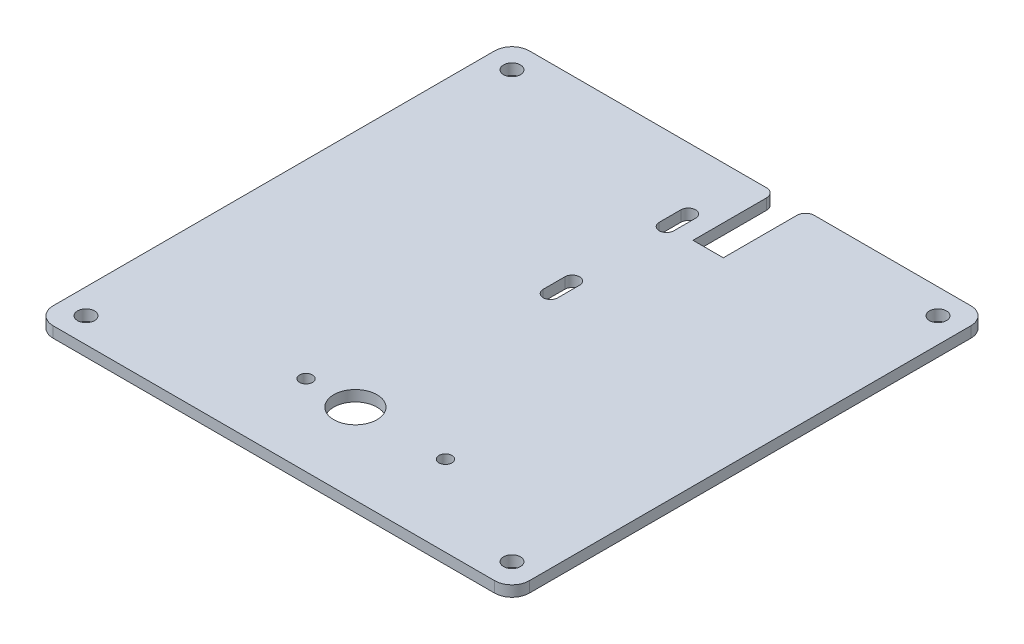
SolidWorks part; units mm, degrees
ref_plane "Front Plane" through (0, 0, 0) normal (0, 0, 1) x (1, 0, 0)
ref_plane "Top Plane" through (0, 0, 0) normal (0, 1, 0) x (1, 0, 0)
ref_plane "Right Plane" through (0, 0, 0) normal (1, 0, 0) x (0, 0, -1)
sketch "Sketch1" plane through (0, 0, 0) normal (0, 1, 0) x (1, 0, 0)
  line L5 (-69.85, -69.85) -> (69.85, -69.85)
  line L6 (-69.85, -69.85) -> (-69.85, 69.85)
  line L7 (-69.85, 69.85) -> (69.85, 69.85)
  line L8 (69.85, -69.85) -> (69.85, 69.85)
  line L9 (-69.85, -69.85) -> (69.85, 69.85) construction
  line L10 (-69.85, 69.85) -> (69.85, -69.85) construction
  line L11 (-69.85, 69.85) -> (69.85, 69.85)
  circle A0 centre (62.484, -62.484) radius 2.4892
  circle A1 centre (62.484, -62.484) radius 7.366 construction
  circle A8 centre (-62.484, 62.484) radius 2.4892
  circle A9 centre (-62.484, 62.484) radius 7.366 construction
  circle A10 centre (62.484, 62.484) radius 2.4892
  circle A11 centre (62.484, 62.484) radius 7.366 construction
  circle A12 centre (-62.484, -62.484) radius 2.4892
  circle A13 centre (-62.484, -62.484) radius 7.366 construction
  dimension "D3" = 14.732
  dimension "D4" = 4.9784
  dimension "D13" = 4.9784
  dimension "D14" = 14.732
  dimension "D15" = 4.9784
  dimension "D16" = 14.732
  dimension "D17" = 4.9784
  dimension "D18" = 14.732
  dimension "D11" = 139.7
  dimension "D12" = 139.7
extrude "Boss-Extrude1" add sketch "Sketch1" along normal blind 3.175 contours L5 L8 L7 L6 A12 A10 A8 A0 region at (0, 0, 0)
sketch "Sketch2" plane through (0, 3.175, 0) normal (0, 1, 0) x (1, 0, 0)
  line L0 (0, 123.83) -> (0, 28.326) construction
  line L1 (-69.85, 69.85) -> (69.85, 69.85)
  line L2 (-69.85, 69.85) -> (-69.85, 123.83) construction
  line L3 (-69.85, 123.83) -> (69.85, 123.83) construction
  line L4 (69.85, 69.85) -> (69.85, 123.83) construction
  line L5 (0, 11.308) -> (0, 45.344) construction
  line L6 (0, 45.344) -> (0, 51.694) construction
  line L7 (-2.1527, 45.344) -> (-2.1527, 51.694)
  line L8 (2.1527, 45.344) -> (2.1527, 51.694)
  line L9 (0, 11.308) -> (0, 17.658) construction
  line L10 (-2.1526, 11.308) -> (-2.1526, 17.658)
  line L11 (2.1527, 11.308) -> (2.1527, 17.658)
  line L12 (16.2727, 69.85) -> (7.3827, 69.85)
  line L13 (7.3827, 69.85) -> (16.2727, 69.85)
  line L14 (7.3827, 69.85) -> (7.3827, 45.72)
  line L15 (7.3827, 45.72) -> (16.2727, 45.72)
  line L16 (16.2727, 69.85) -> (16.2727, 45.72)
  arc A0 (-2.1527, 45.344) -> (2.1527, 45.344) centre (0, 45.344) ccw
  arc A1 (2.1527, 51.694) -> (-2.1527, 51.694) centre (0, 51.694) ccw
  arc A2 (-2.1526, 11.308) -> (2.1527, 11.308) centre (0, 11.308) ccw
  arc A3 (2.1527, 17.658) -> (-2.1526, 17.658) centre (0, 17.658) ccw
  point P10 (0, 48.519)
  point P16 (0, 14.483)
  dimension "D6" = 4.3053
  dimension "D7" = 4.3053
  dimension "D1" = 95.504
  dimension "D2" = 53.98
  dimension "D3" = 34.036
  dimension "D4" = 6.35
  dimension "D5" = 6.35
  dimension "D8" = 5.23
  dimension "D9" = 8.89
  dimension "D10" = 24.13
extrude "Cut-Extrude2" cut sketch "Sketch2" against normal up to surface (3.175 mm away) contours L16 L1 L14 L15 | A0 L8 A1 L7 | A3 L10 A2 L11 region at (11.8277, 3.175, -57.785) up to face at (-62.484, 0, 64.9732)
sketch "Sketch3" plane through (0, 3.175, 0) normal (0, 1, 0) x (1, 0, 0)
  line L0 (69.85, -69.85) -> (69.85, 69.85) construction
  line L1 (-69.85, -69.85) -> (69.85, -69.85) construction
  line L2 (-69.85, -69.85) -> (-69.85, -46.1981) construction
  line L3 (-69.85, -46.1981) -> (69.85, -46.1981) construction
  line L4 (69.85, -69.85) -> (69.85, -46.1981) construction
  circle A0 centre (-14.224, -46.1981) radius 1.905
  circle A1 centre (26.67, -46.1981) radius 1.905
  circle A2 centre (0.254, -46.1981) radius 6.35
  dimension "D4" = 3.81
  dimension "D5" = 3.81
  dimension "D6" = 12.7
  dimension "D1" = 23.6519
  dimension "D2" = 40.894
  dimension "D3" = 14.478
  dimension "D7" = 43.18
extrude "Cut-Extrude4" cut sketch "Sketch3" against normal up to surface (3.175 mm away) contours A2 | A1 | A0 region at (26.67, 3.175, 46.1981) region at (0.254, 3.175, 46.1981) up to face at (0, 0, -48.519)
fillet "Fillet2" radius 5.08 1 edges at (-69.85, 1.5875, 69.85) type face fillet first side face at (-69.85, 1.5875, 0) second side face at (0, 1.5875, 69.85)
fillet "Fillet3" radius 5.08 1 edges at (69.85, 1.5875, 69.85) type face fillet first side face at (69.85, 1.5875, 0) second side face at (2.54, 1.5875, 69.85)
fillet "Fillet4" radius 5.08 1 edges at (69.85, 1.5875, -69.85) type face fillet first side face at (43.0613, 1.5875, -69.85) second side face at (69.85, 1.5875, -2.54)
fillet "Fillet5" radius 5.08 1 edges at (-69.85, 1.5875, -69.85) type face fillet first side face at (-69.85, 1.5875, -2.54) second side face at (-31.2337, 1.5875, -69.85)
fillet "Fillet6" radius 2.54 1 edges at (7.3827, 1.5875, -69.85) type face fillet first side face at (-28.6937, 1.5875, -69.85) second side face at (7.3827, 1.5875, -57.785)
fillet "Fillet8" radius 2.54 1 edges at (16.2727, 1.5875, -69.85) type face fillet first side face at (16.2727, 1.5875, -57.785) second side face at (40.5213, 1.5875, -69.85)
